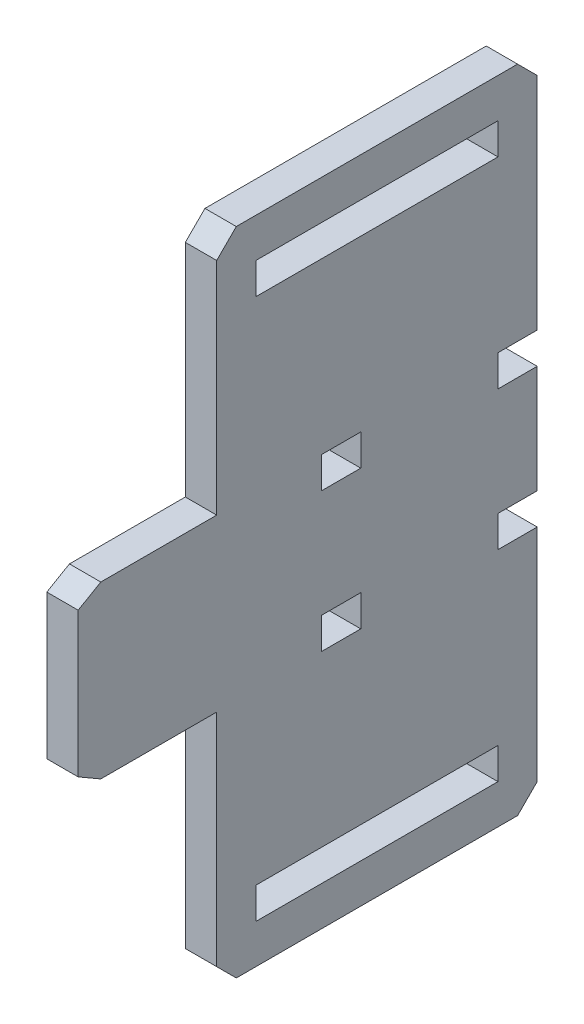
SolidWorks part; units mm, degrees
ref_plane "Front" through (0, 0, 0) normal (0, 0, 1) x (1, 0, 0)
ref_plane "Top" through (0, 0, 0) normal (0, 1, 0) x (1, 0, 0)
ref_plane "Right" through (0, 0, 0) normal (1, 0, 0) x (0, 0, -1)
ref_axis "side-side" through (80.9, 0, 0) along (-1, 0, 0)
ref_axis "up-down" through (0, 50, 0) along (0, -1, 0)
ref_axis "front-back" through (0, 0, -80.9) along (0, 0, 1)
sketch "Sketch1" plane through (0, 0, 0) normal (1, 0, 0) x (0, 0, -1)
  line L1 (38.1, -49.53) -> (-8.9519, -49.53)
  line L2 (45.72, -63.246) -> (45.72, -16.5735)
  line L3 (38.1, 49.53) -> (-8.9519, 49.53)
  line L4 (-43.4959, -14.0335) -> (-43.4959, 14.0335)
  line L5 (109.3291, 0) -> (45.72, 0) construction
  line L8 (45.72, -54.61) -> (38.1, -54.61) construction
  line L9 (38.1, 49.53) -> (38.1, 55.626)
  line L10 (38.1, 54.61) -> (45.72, 54.61) construction
  line L11 (50, 0) -> (-50, 0) construction
  line L12 (-16.5719, 54.61) -> (-8.9519, 54.61) construction
  line L13 (38.1, 16.5735) -> (45.72, 16.5735)
  line L14 (38.1, -55.626) -> (38.1, -49.53)
  line L15 (-8.9519, 55.626) -> (-8.9519, 49.53)
  line L16 (-16.5719, -54.61) -> (-8.9519, -54.61) construction
  line L17 (38.1, 16.5735) -> (38.1, 10.4775)
  line L18 (38.1, 10.4775) -> (45.72, 10.4775)
  line L19 (-8.9519, -55.626) -> (-8.9519, -49.53)
  line L20 (45.72, 16.5735) -> (45.72, 63.246)
  line L21 (38.1, -10.4775) -> (45.72, -10.4775)
  line L22 (38.1, -10.4775) -> (38.1, -16.5735)
  line L23 (38.1, -16.5735) -> (45.72, -16.5735)
  line L25 (11.43, 16.5735) -> (3.81, 16.5735)
  line L26 (11.43, 16.5735) -> (11.43, 10.4775)
  line L27 (11.43, 10.4775) -> (3.81, 10.4775)
  line L28 (3.81, 16.5735) -> (3.81, 10.4775)
  line L29 (3.81, -16.5735) -> (11.43, -16.5735)
  line L30 (3.81, -16.5735) -> (3.81, -10.4775)
  line L31 (3.81, -10.4775) -> (11.43, -10.4775)
  line L32 (11.43, -16.5735) -> (11.43, -10.4775)
  line L33 (45.72, 16.5735) -> (45.72, 10.4775) construction
  line L34 (45.72, -10.4775) -> (45.72, 10.4775)
  line L35 (-16.5719, 63.246) -> (-16.5719, 16.5735)
  line L36 (-16.5719, -63.246) -> (-16.5719, -16.5735)
  line L37 (-16.5719, 16.5735) -> (-39.0964, 16.5735)
  line L38 (-16.5719, -16.5735) -> (-39.0964, -16.5735)
  line L39 (-39.0964, 16.5735) -> (-43.4959, 14.0335)
  line L40 (-39.0964, -16.5735) -> (-43.4959, -14.0335)
  line L41 (45.72, 63.246) -> (-16.5719, 63.246)
  line L42 (38.1, 55.626) -> (-8.9519, 55.626) construction
  line L43 (38.1, 55.626) -> (-8.9519, 55.626)
  line L44 (38.1, -55.626) -> (-8.9519, -55.626) construction
  line L45 (38.1, -55.626) -> (-8.9519, -55.626)
  line L46 (45.72, -63.246) -> (-16.5719, -63.246)
  dimension "D1" = 49.53
  dimension "D2" = 5.08
  dimension "D3" = 26.924
  dimension "D4" = 30
  dimension "D5" = 2.54
  dimension "D6" = 7.62
  dimension "D7" = 7.62
extrude "Boss-Extrude1" add sketch "Sketch1" along normal mid plane 6.096
chamfer "Chamfer2" distance 3.81 angle 45 4 edges at (0, -63.246, -45.72) (0, -63.246, 16.5719) (0, 63.246, -45.72) (0, 63.246, 16.5719)
